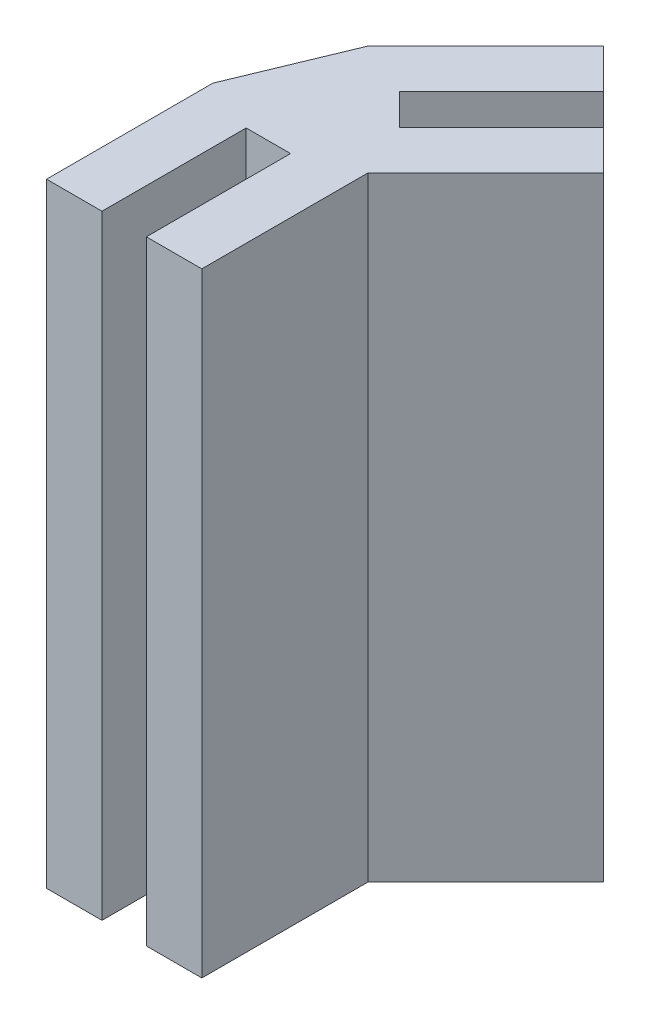
SolidWorks part; units mm, degrees
ref_plane "Front Plane" through (0, 0, 0) normal (0, 0, 1) x (1, 0, 0)
ref_plane "Top Plane" through (0, 0, 0) normal (0, 1, 0) x (1, 0, 0)
ref_plane "Right Plane" through (0, 0, 0) normal (1, 0, 0) x (0, 0, -1)
sketch "Sketch2" plane through (0, 0, 0) normal (0, 1, 0) x (1, 0, 0)
  line L0 (0, 0) -> (0, -15)
  line L1 (0, -15) -> (-5, -15)
  line L2 (-5, -15) -> (-5, -2)
  line L3 (-5, -2) -> (-9, -2)
  line L4 (-9, -2) -> (-9, -15)
  line L5 (-9, -15) -> (-14, -15)
  line L6 (0, 0) -> (-14, 5.799)
  line L7 (-14, -15) -> (-14, 5.799)
extrude "Boss-Extrude1" add sketch "Sketch2" along normal blind 55.3741
ref_plane "Plane1" through (0, 0, 0) normal (0.3827, 0, -0.9239) x (-0.9239, 0, -0.3827)
mirror "Mirror2" about plane through (0, 55.3741, 0) normal (-0.3827, 0, 0.9239) of "Boss-Extrude1"
fillet "Chamfer1" radius 14 1 edges at (-14, 27.687, -5.799) type face fillet profile chamfer first side face at (-6.6464, 27.687, -13.1525) second side face at (-14, 27.687, 4.6005)
ref_axis "Axis1" through (0, 55.3741, 0) along (-0.9239, 0, -0.3827)
